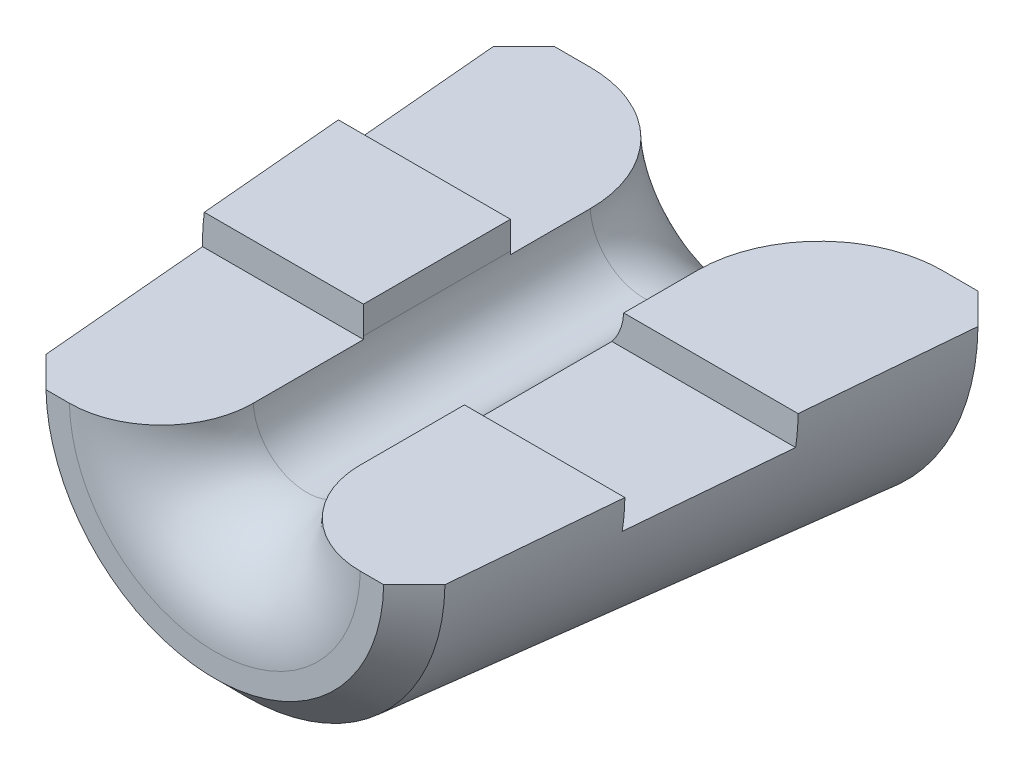
SolidWorks part; units mm, degrees
ref_plane "Front" through (0, 0, 0) normal (0, 0, 1) x (1, 0, 0)
ref_plane "Top" through (0, 0, 0) normal (0, 1, 0) x (1, 0, 0)
ref_plane "Right" through (0, 0, 0) normal (1, 0, 0) x (0, 0, -1)
sketch "Sketch2" plane through (0, 0, 0) normal (1, 0, 0) x (0, 0, -1)
  line L0 (0, 0) -> (-18, 0)
  line L1 (-18, 0) -> (-18, 5.5127)
  line L2 (-18, 5.5127) -> (-17, 6.5127)
  line L3 (-17, 6.5127) -> (-1, 7.9125)
  line L4 (-1, 7.9125) -> (0, 6.9125)
  line L5 (0, 6.9125) -> (0, 0)
  line L9 (-18, 5.5127) -> (-18, 6.4252) construction
  line L10 (-18, 6.4252) -> (-17, 6.5127) construction
  line L11 (-1, 7.9125) -> (0, 8) construction
  line L12 (0, 8) -> (0, 6.9125) construction
  line L13 (-18, 0) -> (-20.4063, 0) construction
  dimension "D1" = 45
  dimension "D2" = 45
  dimension "D3" = 1
  dimension "D4" = 1
  dimension "D5" = 18
  dimension "D6" = 16
  dimension "D7" = 5
revolve "Body Revolve1" add sketch "Sketch2" angle 360 about L13
sketch "Sketch3" plane through (0, 0, 0) normal (0, 0, 1) x (1, 0, 0)
  circle A0 centre (0, 0) radius 1.75
  dimension "D1" = 3.5
extrude "Wire Hole Cut" cut sketch "Sketch3" along normal through all
fillet "Front Strain Fillet" radius 3 1 edges at (1.75, 0, 18)
fillet "Rear Strain Fillet" radius 4 1 edges at (1.75, 0, 0)
sketch "Sketch5" plane through (0, 0, 0) normal (1, 0, 0) x (0, 0, -1)
  line L0 (-18, 0) -> (-11.5, 0)
  line L2 (-11.5, 0) -> (-6.5, 0) construction
  line L3 (-6.5, 0) -> (0, 0)
  line L4 (-11.5, 0) -> (-11.5, 1)
  line L5 (-11.5, 1) -> (-6.5, 1)
  line L6 (-6.5, 1) -> (-6.5, 0)
  line L7 (-18, 5.5127) -> (-18, 6.4252) construction
  dimension "D1" = 1
  dimension "D2" = 5
extrude "Split Cut 1" cut sketch "Sketch5" against normal through all thin thin type one direction wall 0.1
sketch "Sketch7" plane through (0, 0, 0) normal (1, 0, 0) x (0, 0, -1)
  line L0 (-18, 0) -> (-11.5, 0)
  line L1 (-11.5, 0) -> (-11.5, -1)
  line L2 (-11.5, -1) -> (-6.5, -1)
  line L3 (-6.5, -1) -> (-6.5, 0)
  line L4 (-6.5, 0) -> (0, 0)
  line L5 (-11.5, 0) -> (-11.5, 1) construction
extrude "Split Cut 2" cut sketch "Sketch7" along normal through all thin body kept at (-1.7471, -0.1, 4) thin type one direction wall 0.1
sketch "Sketch6" plane through (0, 0, 0) normal (0, 0, 1) x (1, 0, 0)
  line L0 (-1.75, 0) -> (-1.75, 2)
  line L2 (-1.75, 2) -> (1.75, 2)
  line L3 (1.75, 2) -> (1.75, 0)
  circle A0 centre (0, 0) radius 1.75 construction
  arc A1 (-1.75, 0) -> (1.75, 0) centre (0, 0) ccw
  dimension "D1" = 2
extrude "Wire Insert Notch" cut sketch "Sketch6" along normal through all
